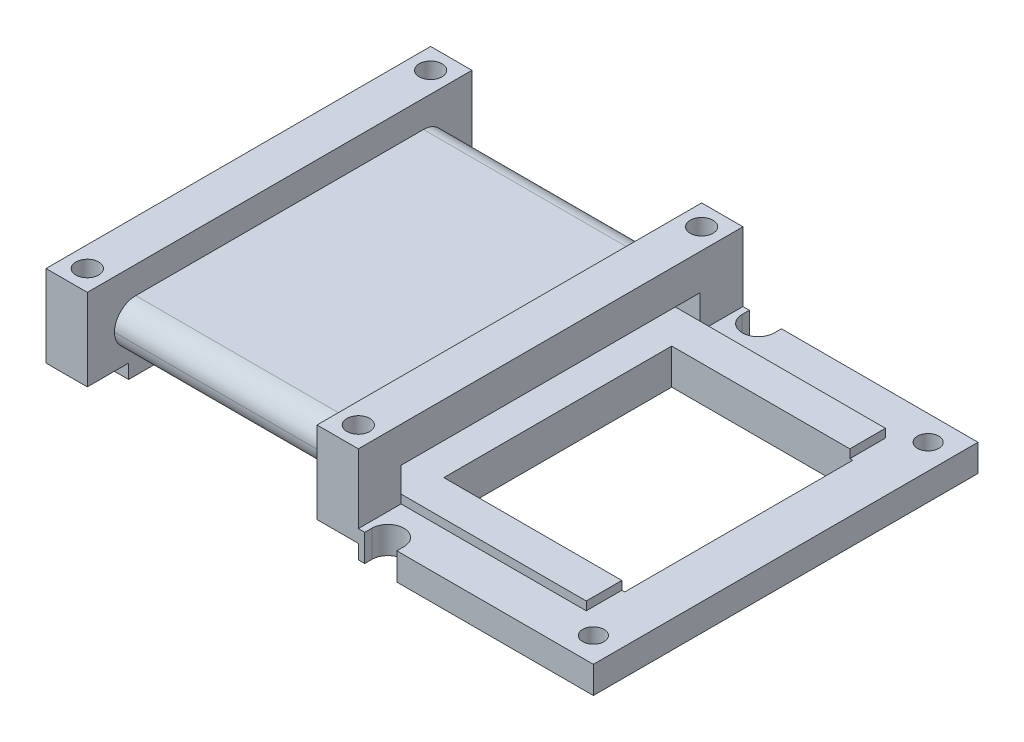
SolidWorks part; units mm, degrees
ref_plane "Front Plane" through (0, 0, 0) normal (0, 0, 1) x (1, 0, 0)
ref_plane "Top Plane" through (0, 0, 0) normal (0, 1, 0) x (1, 0, 0)
ref_plane "Right Plane" through (0, 0, 0) normal (1, 0, 0) x (0, 0, -1)
sketch "Sketch1" plane through (0, 0, 0) normal (1, 0, 0) x (0, 0, -1)
  line L0 (23.2, 5.9) -> (23.2, 0) construction
  line L1 (0, 0) -> (46.4, 0)
  line L2 (0, 0) -> (0, 5.9)
  line L3 (0, 5.9) -> (46.4, 5.9)
  line L4 (46.4, 0) -> (46.4, 5.9)
  line L6 (2.2, 1.2) -> (44.2, 1.2)
  line L7 (2.2, 1.2) -> (2.2, 4.7)
  line L8 (2.2, 4.7) -> (44.2, 4.7)
  line L9 (44.2, 1.2) -> (44.2, 4.7)
  line L10 (2.2, 1.2) -> (44.2, 4.7) construction
  line L11 (2.2, 4.7) -> (44.2, 1.2) construction
  point P7 (23.2, 2.95)
  dimension "D1" = 46.4
  dimension "D2" = 5.9
  dimension "D3" = 3.5
  dimension "D4" = 42
extrude "Boss-Extrude1" add sketch "Sketch1" along normal blind 32.25
fillet "Fillet2" radius 3 4 edges at (16.125, 0, -46.4) (16.125, 0, 0) (16.125, 5.9, 0) (16.125, 5.9, -46.4)
sketch "Sketch2" plane through (32.25, 0, 0) normal (1, 0, 0) x (0, 0, -1)
  line L0 (23.2, 5.9) -> (23.2, 0) construction
  line L1 (43.4, 5.9) -> (3, 5.9) construction
  line L2 (3, 0) -> (43.4, 0) construction
  line L4 (-3.8, -3.8) -> (50.2, -3.8)
  line L5 (-3.8, -3.8) -> (-3.8, 9.7)
  line L6 (-3.8, 9.7) -> (50.2, 9.7)
  line L7 (50.2, -3.8) -> (50.2, 9.7)
  line L8 (-3.8, -3.8) -> (50.2, 9.7) construction
  line L9 (-3.8, 9.7) -> (50.2, -3.8) construction
  line L14 (44.2, 1.2) -> (2.2, 1.2)
  line L15 (44.2, 1.2) -> (44.2, 4.7)
  line L16 (44.2, 4.7) -> (2.2, 4.7)
  line L17 (2.2, 1.2) -> (2.2, 4.7)
  line L18 (44.2, 1.2) -> (2.2, 4.7) construction
  line L19 (44.2, 4.7) -> (2.2, 1.2) construction
  point P6 (23.2, 2.95)
  point P11 (23.2, 2.95)
  point P12 (23.2, 2.95)
  dimension "D1" = 13.5
  dimension "D2" = 54
extrude "Boss-Extrude2" add sketch "Sketch2" along normal blind 5.8
sketch "Sketch3" plane through (0, 0, 0) normal (-1, 0, 0) x (0, 0, 1)
  line L0 (-23.2, 5.9) -> (-23.2, 0) construction
  line L1 (-43.4, 5.9) -> (-3, 5.9) construction
  line L2 (-3, 0) -> (-43.4, 0) construction
  line L4 (3.8, -3.8) -> (-50.2, -3.8)
  line L5 (3.8, -3.8) -> (3.8, 9.7)
  line L6 (3.8, 9.7) -> (-50.2, 9.7)
  line L7 (-50.2, -3.8) -> (-50.2, 9.7)
  line L8 (3.8, -3.8) -> (-50.2, 9.7) construction
  line L9 (3.8, 9.7) -> (-50.2, -3.8) construction
  line L10 (-2.2, 1.2) -> (-44.2, 1.2)
  line L11 (-2.2, 1.2) -> (-2.2, 4.7)
  line L12 (-2.2, 4.7) -> (-44.2, 4.7)
  line L13 (-44.2, 1.2) -> (-44.2, 4.7)
  line L14 (-2.2, 1.2) -> (-44.2, 4.7) construction
  line L15 (-2.2, 4.7) -> (-44.2, 1.2) construction
  point P6 (-23.2, 2.95)
  point P12 (-23.2, 2.95)
extrude "Boss-Extrude3" add sketch "Sketch3" along normal blind 5.8
sketch "Sketch4" plane through (0, 9.7, 0) normal (0, 1, 0) x (1, 0, 0)
  line L0 (-2.9, 50.2) -> (-2.9, 47.3) construction
  line L1 (-5.8, 50.2) -> (0, 50.2) construction
  line L2 (35.15, 50.2) -> (35.15, 47.3) construction
  line L3 (38.05, 50.2) -> (32.25, 50.2) construction
  line L4 (-2.9, -3.8) -> (-2.9, -0.9) construction
  line L5 (-5.8, -3.8) -> (0, -3.8) construction
  line L6 (35.15, -3.8) -> (35.15, -0.9) construction
  line L7 (38.05, -3.8) -> (32.25, -3.8) construction
  circle A0 centre (-2.9, 47.3) radius 1.6
  circle A1 centre (35.15, 47.3) radius 1.6
  circle A2 centre (-2.9, -0.9) radius 1.6
  circle A3 centre (35.15, -0.9) radius 1.6
  dimension "D2" = 3.2
  dimension "D4" = 3.2
  dimension "D6" = 3.2
  dimension "D8" = 3.2
  dimension "D1" = 2.9
  dimension "D3" = 2.9
  dimension "D5" = 2.9
  dimension "D7" = 2.9
extrude "Cut-Extrude1" cut sketch "Sketch4" against normal through all
sketch "Sketch6" plane through (38.05, 0, 0) normal (1, 0, 0) x (0, 0, -1)
  line L0 (50.2, -3.8) -> (50.2, 9.7) construction
  line L1 (-3.8, -3.8) -> (50.2, -3.8)
  line L2 (-3.8, -3.8) -> (-3.8, 3.4)
  line L3 (-3.8, 3.4) -> (50.2, 3.4)
  line L4 (50.2, -3.8) -> (50.2, 3.4)
  dimension "D1" = 7.2
extrude "Cut-Extrude2" [suppressed] cut sketch "Sketch6" against normal blind 5.8
sketch "Sketch7" plane through (-5.8, 0, 0) normal (-1, 0, 0) x (0, 0, 1)
  line L0 (3.8, -3.8) -> (3.8, 9.7) construction
  line L1 (-50.2, -3.8) -> (3.8, -3.8)
  line L2 (-50.2, -3.8) -> (-50.2, 3.4)
  line L3 (-50.2, 3.4) -> (3.8, 3.4)
  line L4 (3.8, -3.8) -> (3.8, 3.4)
  dimension "D1" = 7.2
extrude "Cut-Extrude3" [suppressed] cut sketch "Sketch7" against normal blind 5.8
sketch "Sketch15" plane through (-5.8, 0, 0) normal (-1, 0, 0) x (0, 0, 1)
  line L1 (-44.2, 1.2) -> (-2.2, 1.2)
  line L2 (-44.2, 1.2) -> (-44.2, 4.7)
  line L3 (-44.2, 4.7) -> (-2.2, 4.7)
  line L4 (-2.2, 1.2) -> (-2.2, 4.7)
  line L5 (-50.2, -3.8) -> (-44.4, -3.8)
  line L6 (-50.2, -3.8) -> (-50.2, -1.8)
  line L7 (-50.2, -1.8) -> (-44.4, -1.8)
  line L8 (-44.4, -3.8) -> (-44.4, -1.8)
  line L9 (3.8, -3.8) -> (-2, -3.8)
  line L10 (3.8, -3.8) -> (3.8, -1.8)
  line L11 (3.8, -1.8) -> (-2, -1.8)
  line L12 (-2, -3.8) -> (-2, -1.8)
  dimension "D1" = 5.8
  dimension "D2" = 2
  dimension "D3" = 5.8
  dimension "D4" = 2
extrude "Cut-Extrude5" cut sketch "Sketch15" against normal through all
fillet "Fillet3" radius 2 1 edges at (-5.8, -3.8, -23.2)
sketch "Sketch16" plane through (38.05, 0, 0) normal (1, 0, 0) x (0, 0, -1)
  line L0 (-3.8, -3.8) -> (50.2, -3.8)
  line L1 (50.2, 0) -> (-3.8, 0)
  line L2 (2, -3.8) -> (44.4, -3.8) construction
  line L3 (-3.8, 9.7) -> (-3.8, -1.8) construction
  line L4 (2.2, 1.2) -> (2.2, 0)
  line L5 (50.2, -3.8) -> (50.2, 0)
  line L6 (-3.8, 0) -> (-3.8, -3.8)
  line L7 (2.2, 1.2) -> (44.2, 1.2)
  line L8 (44.2, 1.2) -> (44.2, 0)
  point P5 (23.2, 0)
  point P6 (23.2, -3.8)
  line M5 (44.4, -3.8) -> (44.4, -1.8)
  line M6 (44.4, -1.8) -> (50.2, -1.8)
  line M7 (50.2, -1.8) -> (50.2, 9.7)
  line M9 (-3.8, 9.7) -> (-3.8, -1.8)
  line M10 (-3.8, -1.8) -> (2, -1.8)
  line M11 (2, -1.8) -> (2, -3.8)
  line M12 (2, -3.8) -> (44.4, -3.8)
  line M16 (44.2, 1.2) -> (2.2, 1.2)
  dimension "D1" = 3.8
extrude "Boss-Extrude4" add sketch "Sketch16" along normal blind 26 contours L8 L4 L1 M16 region at (38.05, 0.6, -23.2)
extrude "Boss-Extrude5" add sketch "Sketch16<3>" along normal blind 30 contours L1 M7 M9 M10 M11 M12 M5 M6 | L6 L0 M10 M11 | L0 L5 M6 M5 region at (38.05, -2.8, 0.9) region at (38.05, -1.7853, -23.2) region at (38.05, -2.8, -47.3)
sketch "Sketch16<3>" plane through (38.05, 0, 0) normal (1, 0, 0) x (0, 0, -1) same geometry as "Sketch16"
sketch "Sketch17" plane through (0, 1.2, 0) normal (0, 1, 0) x (1, 0, 0)
  line L0 (68.05, 50.2) -> (68.05, 39.2) construction
  line L2 (39.05, 39.2) -> (68.05, 39.2)
  line L3 (68.05, 7.2) -> (68.05, -3.8) construction
  line L4 (68.05, 39.2) -> (68.05, 7.2)
  line L5 (68.05, 7.2) -> (39.05, 7.2)
  line L7 (39.05, 39.2) -> (39.05, 7.2)
  line L10 (68.05, 50.2) -> (68.05, -3.8) construction
  dimension "D1" = 11
  dimension "D2" = 11
  dimension "D3" = 29
extrude "Cut-Extrude6" cut sketch "Sketch17" against normal blind 10
sketch "Sketch18" plane through (0, -3.8, 0) normal (0, -1, 0) x (1, 0, 0)
  line L0 (38.05, 3.8) -> (38.05, 2.8) construction
  line L1 (38.05, 3.8) -> (38.05, -2) construction
  line L2 (38.05, 2.8) -> (41.2, 2.8) construction
  line L3 (38.95, 2.8) -> (38.95, 3.8)
  line L4 (68.05, 3.8) -> (38.05, 3.8) construction
  line L5 (43.45, 2.8) -> (43.45, 3.8)
  line L6 (38.05, -50.2) -> (38.05, -49.2) construction
  line L7 (38.05, -44.4) -> (38.05, -50.2) construction
  line L8 (38.05, -49.2) -> (41.2, -49.2) construction
  line L9 (38.95, -49.2) -> (38.95, -50.2)
  line L12 (43.45, -49.2) -> (43.45, -50.2)
  line L15 (43.45, -50.2) -> (43.2156, -50.2)
  line L18 (68.05, -50.2) -> (38.05, -50.2) construction
  line L19 (38.95, -50.2) -> (39.1844, -50.2)
  line L20 (43.45, 3.8) -> (43.2156, 3.8)
  line L21 (38.95, 3.8) -> (39.1844, 3.8)
  circle A0 centre (41.2, 2.8) radius 2.25
  circle A1 centre (41.2, -49.2) radius 2.25
  line M8 (68.05, 3.8) -> (38.05, 3.8)
  line M14 (38.05, -50.2) -> (68.05, -50.2)
  dimension "D3" = 4.5
  dimension "D6" = 4.5
  dimension "D1" = 1
  dimension "D2" = 3.15
  dimension "D4" = 3.15
  dimension "D5" = 1
  dimension "D7" = 1
  dimension "D8" = 1
extrude "Cut-Extrude7" cut sketch "Sketch18" against normal blind 30 contours A0 M8 | A0 L3 M8 | A0 L5 M8 | A1 M14 | A1 L9 M14 | A1 L12 M14 region at (39.0197, -3.8, 3.5527) region at (41.2, -3.8, 2.3562) region at (43.3803, -3.8, 3.5527) region at (39.0197, -3.8, -49.9527) region at (41.2, -3.8, -48.7562) region at (43.3803, -3.8, -49.9527)
sketch "Sketch19" plane through (0, -3.8, 0) normal (0, -1, 0) x (1, 0, 0)
  line L0 (68.05, 3.8) -> (68.05, -50.2)
  line L1 (68.05, 3.8) -> (71.05, 3.8)
  line L2 (68.05, -50.2) -> (71.05, -50.2)
  line L3 (71.05, 3.8) -> (71.05, -50.2)
  line L4 (68.05, -7.2) -> (68.05, -39.2)
  line L5 (68.05, -7.2) -> (64.45, -7.2)
  line L6 (68.05, -39.2) -> (64.45, -39.2)
  line L7 (64.45, -7.2) -> (64.45, -39.2)
  line M18 (68.05, -50.2) -> (68.05, -39.2)
  line M19 (68.05, -39.2) -> (39.05, -39.2)
  line M21 (39.05, -7.2) -> (68.05, -7.2)
  line M22 (68.05, -7.2) -> (68.05, 3.8)
  dimension "D1" = 3
  dimension "D2" = 3.6
extrude "Boss-Extrude6" add sketch "Sketch19" against normal up to surface (3.8 mm away) contours L7 L0 M21 M19 | L3 L1 L0 L2 M22 M18 region at (69.55, -3.8, -23.2) region at (66.25, -3.8, -23.2) up to face at (50.51, 0, -0.025)
sketch "Sketch20" plane through (0, 0, 0) normal (0, 1, 0) x (1, 0, 0)
  line L0 (71.05, -3.8) -> (67.55, -3.8)
  line L1 (71.05, -3.8) -> (43.45, -3.8) construction
  line L2 (67.55, -3.8) -> (67.55, -0.3)
  line L3 (71.05, 50.2) -> (67.55, 50.2)
  line L4 (71.05, 50.2) -> (43.45, 50.2) construction
  line L5 (67.55, 50.2) -> (67.55, 46.7)
  circle A0 centre (67.55, -0.3) radius 1.5
  circle A1 centre (67.55, 46.7) radius 1.5
  dimension "D3" = 3
  dimension "D6" = 3
  dimension "D1" = 3.5
  dimension "D2" = 3.5
  dimension "D4" = 3.5
  dimension "D5" = 3.5
extrude "Cut-Extrude8" cut sketch "Sketch20" against normal through all contours A1 | A0 region at (68.5807, 0, 1.3307) region at (66.5193, 0, -45.6693)
